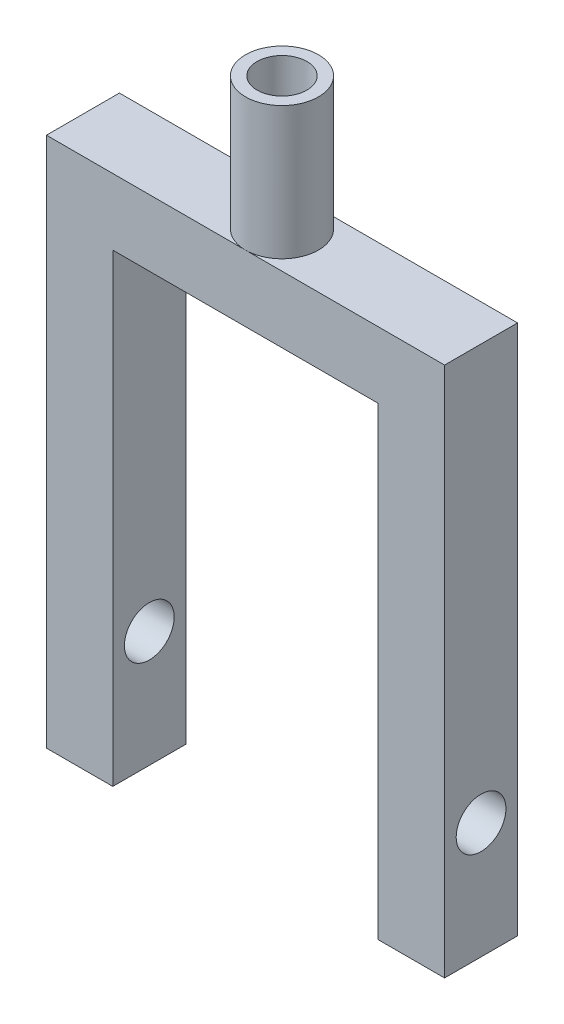
SolidWorks part; units mm, degrees
ref_plane "Front Plane" through (0, 0, 0) normal (0, 0, 1) x (1, 0, 0)
ref_plane "Top Plane" through (0, 0, 0) normal (0, 1, 0) x (1, 0, 0)
ref_plane "Right Plane" through (0, 0, 0) normal (1, 0, 0) x (0, 0, -1)
sketch "Sketch1" plane through (0, 0, 0) normal (0, 1, 0) x (1, 0, 0)
  circle A0 centre (0, 0) radius 6.985
  dimension "D1" = 13.97
extrude "Boss-Extrude1" add sketch "Sketch1" against normal blind 25.4
sketch "Sketch3" plane through (0, 0, 0) normal (0, 1, 0) x (1, 0, 0)
  circle A0 centre (0, 0) radius 4.7625
  circle A1 centre (0, 0) radius 6.985 construction
  point P3 (0, 0)
  dimension "D1" = 9.525
extrude "Cut-Extrude1" cut sketch "Sketch3" against normal blind 63.5
sketch "Sketch4" plane through (0, 0, 0) normal (0, 1, 0) x (1, 0, 0)
  line L0 (6.985, 0) -> (8.8102, 0) construction
  circle A0 centre (0, 0) radius 6.985 construction
  point P6 (0, 0)
  dimension "D1" = 1.8252
sketch "Sketch5" plane through (0, -25.4, 0) normal (0, -1, 0) x (-1, 0, 0)
  line L1 (38.1, -6.985) -> (-38.1, -6.985)
  line L2 (38.1, -6.985) -> (38.1, 6.985)
  line L3 (38.1, 6.985) -> (-38.1, 6.985)
  line L4 (-38.1, -6.985) -> (-38.1, 6.985)
  line L5 (38.1, -6.985) -> (-38.1, 6.985) construction
  line L6 (38.1, 6.985) -> (-38.1, -6.985) construction
  circle A0 centre (0, 0) radius 4.7625 construction
  point P0 (0, 0)
  point P6 (0, 0)
  dimension "D1" = 76.2
  dimension "D2" = 13.97
extrude "Boss-Extrude2" add sketch "Sketch5" along normal blind 101.6
sketch "Sketch6" plane through (0, 0, -6.985) normal (0, 0, -1) x (-1, 0, 0)
  line L0 (0, -25.4) -> (-38.1, -25.4) construction
  line L1 (25.4, -38.1) -> (-25.4, -38.1)
  line L2 (25.4, -38.1) -> (25.4, -127)
  line L3 (25.4, -127) -> (-25.4, -127)
  line L4 (-25.4, -38.1) -> (-25.4, -127)
  line L5 (25.4, -38.1) -> (-25.4, -127) construction
  line L6 (25.4, -127) -> (-25.4, -38.1) construction
  line L7 (38.1, -127) -> (38.1, -25.4) construction
  line L8 (38.1, -127) -> (-38.1, -127) construction
  point P0 (0, -64.4831)
  point P5 (0, 0)
  point P6 (0, 0)
  point P7 (0, 0)
  point P10 (0, -64.4831)
  point P11 (0, -64.4831)
  point P12 (0, 0)
  point P13 (0, 0)
  point P14 (0, -82.55)
  dimension "D1" = 50.8
  dimension "D3" = 12.7
  dimension "D4" = 38.1
extrude "Cut-Extrude2" cut sketch "Sketch6" against normal through all
sketch "Sketch7" plane through (0, 0, 0) normal (0, 1, 0) x (1, 0, 0)
  circle A0 centre (0, 0) radius 4.7625
  dimension "D1" = 9.525
extrude "Cut-Extrude3" cut sketch "Sketch7" against normal through all
sketch "Sketch8" plane through (25.4, 0, 0) normal (-1, 0, 0) x (0, 0, 1)
  line L0 (6.985, -38.1) -> (-6.985, -38.1) construction
  line L1 (-6.985, -38.1) -> (-6.985, -127) construction
  circle A0 centre (0, -104.775) radius 4.7625
  dimension "D1" = 9.525
  dimension "D2" = 66.675
  dimension "D3" = 6.985
extrude "Cut-Extrude4" cut sketch "Sketch8" against normal blind 19.05 and the other way through all
